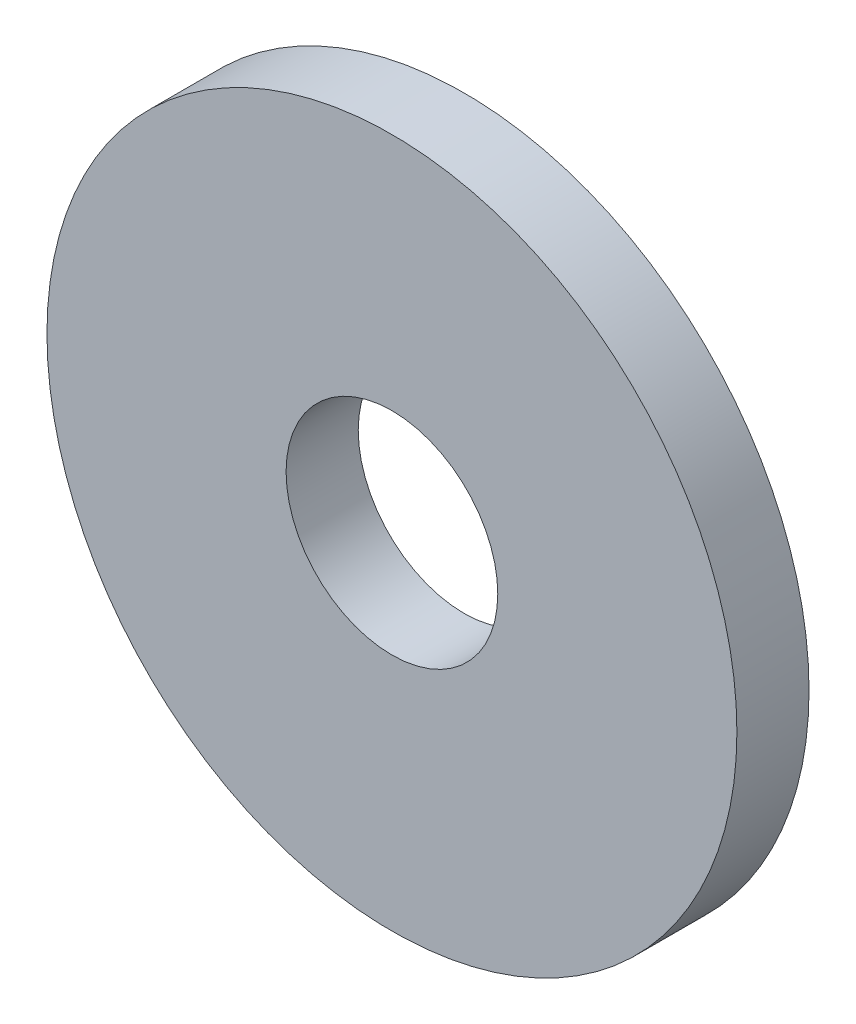
SolidWorks part; units mm, degrees
ref_plane "Front Plane" through (0, 0, 0) normal (0, 0, 1) x (1, 0, 0)
ref_plane "Top Plane" through (0, 0, 0) normal (0, 1, 0) x (1, 0, 0)
ref_plane "Right Plane" through (0, 0, 0) normal (1, 0, 0) x (0, 0, -1)
sketch "Sketch1" plane through (0, 0, 0) normal (0, 0, 1) x (1, 0, 0)
  circle A0 centre (0, 0) radius 22
  circle A1 centre (0, 0) radius 6.75
  dimension "OD" = 44
  dimension "ID1" = 13.5
extrude "Boss-Extrude1" add sketch "Sketch1" along normal blind 4.6
ref_axis "Center Axis 1" through (0, 0, 4.6) along (0, 0, -1)
ref_plane "Contact Plane 1" through (0, 0, 4.6) normal (0, 0, 1) x (1, 0, 0)
ref_plane "Contact Plane 2" through (0, 0, 0) normal (0, 0, -1) x (-1, 0, 0)
